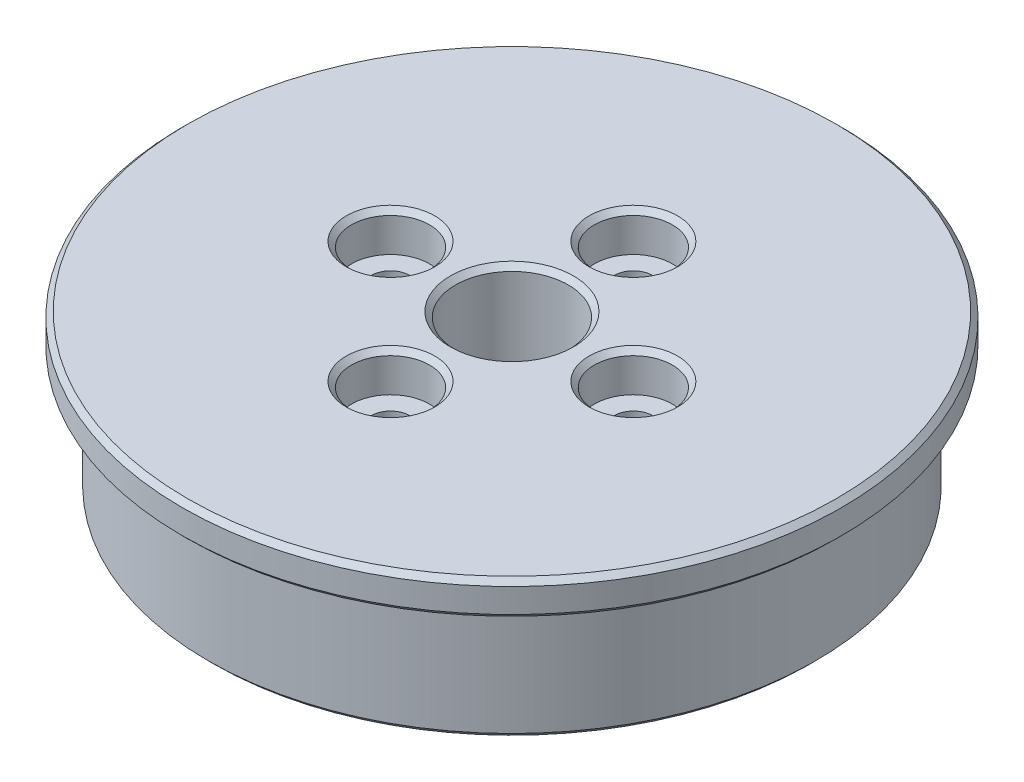
SolidWorks part; units mm, degrees
ref_plane "Front" through (0, 0, 0) normal (0, 0, 1) x (1, 0, 0)
ref_plane "Top" through (0, 0, 0) normal (0, 1, 0) x (1, 0, 0)
ref_plane "Right" through (0, 0, 0) normal (1, 0, 0) x (0, 0, -1)
sketch "Эскиз1" plane through (0, 0, 0) normal (0, 1, 0) x (1, 0, 0)
  circle A0 centre (0, 0) radius 19
  dimension "D1" = 38
extrude "Бобышка-Вытянуть1" add sketch "Эскиз1" along normal blind 10.45
sketch "Эскиз2" plane through (0, 0, 0) normal (0, 1, 0) x (1, 0, 0)
  circle A0 centre (0, 0) radius 10
  circle A1 centre (0, 0) radius 17.5
  circle A2 centre (0, 0) radius 35.8784
  dimension "D1" = 35
  dimension "D2" = 20
extrude "Вырез-Вытянуть1" cut sketch "Эскиз2" along normal blind 1.45 contours A1 A0 | A2 A1 region at (-17.005, 0, 0) region at (-34.8636, 0, 0)
extrude "Вырез-Вытянуть2" cut sketch "Эскиз2<3>" along normal blind 8.45 contours A2 A1 region at (-34.8636, 0, 0)
sketch "Эскиз2<3>" plane through (0, 0, 0) normal (0, 1, 0) x (1, 0, 0) same geometry as "Эскиз2"
sketch "Эскиз3" plane through (0, 0, 0) normal (0, 1, 0) x (1, 0, 0)
  circle A0 centre (0, 0) radius 7 construction
  circle A1 centre (0, 0) radius 3.25
  circle A2 centre (0, 7) radius 1.1
  circle A3 centre (-7, 0) radius 1.1
  circle A4 centre (0, -7) radius 1.1
  circle A5 centre (7, 0) radius 1.1
  circle A6 centre (0, 7) radius 2.25
  circle A7 centre (7, 0) radius 2.25
  circle A8 centre (0, -7) radius 2.25
  circle A9 centre (-7, 0) radius 2.25
  dimension "D1" = 6.5
  dimension "D2" = 14
  dimension "D3" = 2.2
  dimension "D4" = 2.2
  dimension "D5" = 2.2
  dimension "D6" = 2.2
  dimension "D7" = 4.5
  dimension "D8" = 4.5
  dimension "D9" = 4.5
  dimension "D10" = 4.5
extrude "Вырез-Вытянуть3" cut sketch "Эскиз3" along normal through all contours A4 | A3 | A1 | A2 | A5
extrude "Вырез-Вытянуть4" cut sketch "Эскиз3<3>" along normal through all from offset 8.2 contours A9 | A6 | A7 | A8
sketch "Эскиз3<3>" plane through (0, 0, 0) normal (0, 1, 0) x (1, 0, 0) same geometry as "Эскиз3"
sketch "Эскиз4" plane through (0, 0, 0) normal (0, 1, 0) x (1, 0, 0)
  circle A0 centre (0, 0) radius 10
  circle A1 centre (0, 0) radius 16
  dimension "D1" = 32
  dimension "D2" = 20
extrude "Вырез-Вытянуть5" cut sketch "Эскиз4" along normal blind 2.2
sketch "Эскиз5" plane through (0, 0, 0) normal (0, 1, 0) x (1, 0, 0)
  circle A0 centre (0, 0) radius 4.5
extrude "Вырез-Вытянуть6" cut sketch "Эскиз5" along normal blind 2
chamfer "Фаска1" distance 0.3 angle 45 9 edges at (0, 10.45, 19) (0, 10.45, 3.25) (0, 10.45, 9.25) (7, 10.45, 2.25) (0, 10.45, -4.75) (-7, 10.45, 2.25) (0, 1.45, 17.5) (0, 8.45, 19) (0, 0, 4.5)
